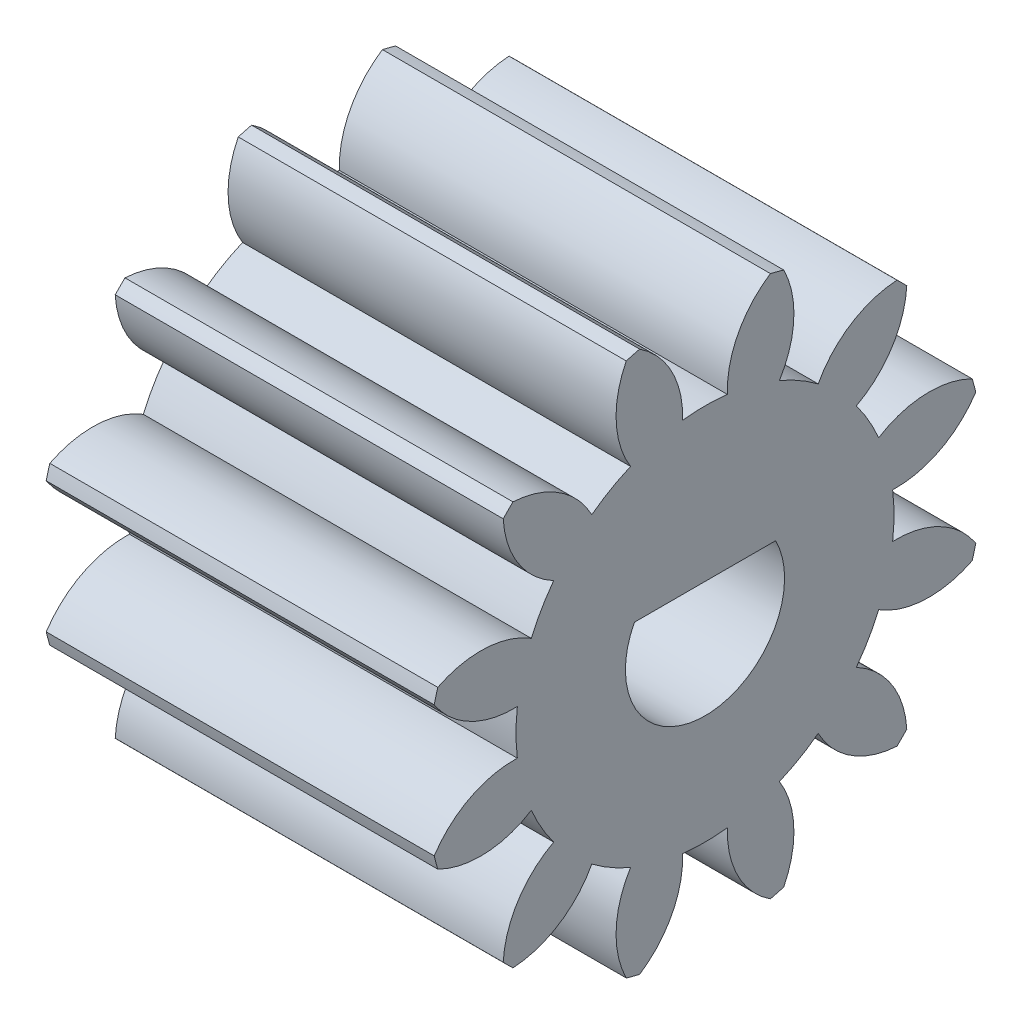
SolidWorks part; units mm, degrees
ref_plane "Plane1" through (0, 0, 0) normal (0, 0, 1) x (1, 0, 0)
ref_plane "Plane2" through (0, 0, 0) normal (0, 1, 0) x (1, 0, 0)
ref_plane "Plane3" through (0, 0, 0) normal (1, 0, 0) x (0, 0, -1)
sketch "HoldingSke" plane through (0, 0, 0) normal (0, 1, 0) x (1, 0, 0)
  line L0 (0, 0) -> (0.9781, -0.2079)
  line L1 (-15, 0) -> (100, 0) construction
  line L2 (0, 0) -> (-2.1039, 2.3779)
  line L3 (0, 0) -> (-11.863, 4.5341)
  line L4 (0, 0) -> (8.4473, 1.7955)
  line L5 (0, 0) -> (-46.8476, -17.4728)
  line L6 (0, 0) -> (-9.9476, -6.7116)
  line L7 (-2.1039, 2.3779) -> (8.6586, 51.2059)
  line L8 (-76.2, 54.61) -> (-76.1, 54.61)
  line L9 (-71.009, 38.7566) -> (-53.1078, 45.2721)
  line L10 (-76.2, 71.12) -> (104.1128, 71.12)
  line L11 (0, 0) -> (-12, 0)
  line L12 (-76.2, 101.6) -> (-76.162, 101.6)
  line L13 (24.9733, 27.94) -> (52.9518, 28.4284)
  line L14 (24.9733, 27.94) -> (24.9743, 27.94)
  line L15 (24.9733, 27.94) -> (100.4006, 29.5858)
  line L16 (-63.627, -1) -> (-12.827, -1)
  circle A0 centre (0, 0) radius 0.4
  circle A1 centre (0, 0) radius 4.749
  circle A2 centre (0, 0) radius 37.5
  circle A3 centre (0, 0) radius 0.4
  dimension "MHD" = 9.498
  dimension "Hub_dia" = 75
  dimension "Bore" = 0.8
  dimension "MBD" = 0.8
  dimension "Num_teeth" = 12
  dimension "Pitch" = 1
  dimension "Overall_len" = 50
  dimension "Show_teeth" = 12
  dimension "Thickness" = 12
  dimension "OAL" = 50.0001
  dimension "T_dim" = 0.1
  dimension "Ap" = 20
  dimension "H" = 19.05
  dimension "Pitch_radius" = 180.3128
  dimension "Width" = 12
  dimension "Backlash" = 0.038
  dimension "Addendum_fac" = 1
  dimension "Dedendum_fac" = 1.25
  dimension "Clearance_fac" = 0.25
  dimension "Dedendum_add" = 0.001
  dimension "Module" = 1
sketch "BasProSke" plane through (0, 0, 0) normal (0, 1, 0) x (1, 0, 0)
  line L0 (-10, 0) -> (60, 0) construction
  line L1 (0, 0) -> (0, 7)
  line L2 (0, 0) -> (9.75, 0)
  line L3 (9.75, 0) -> (9.75, 7)
  line L4 (9.75, 7) -> (0, 7)
  dimension "Thickness" = 9.75
  dimension "Diameter" = 14
revolve "Base-Revolve" add sketch "BasProSke" angle 360 about L0
sketch "TooCutSke" plane through (0, 0, 0) normal (1, 0, 0) x (0, 0, -1)
  line L1 (0, 0) -> (0, 107) construction
  line L2 (0, 0) -> (-0.8496, 5.9395) construction
  line L3 (0, 0) -> (-3.0836, 11.5081) construction
  line L4 (-0.8496, 5.9395) -> (-1.5418, 5.7541) construction
  arc A0 (0.5622, 4.7156) -> (-0.5622, 4.7156) centre (0, 0) ccw
  arc A1 (1.6729, 6.8233) -> (-1.6729, 6.8233) centre (0, 0) ccw
  circle A2 centre (0, 0) radius 6 construction
  circle A3 centre (0, 0) radius 5.6382 construction
  arc A4 (-0.5622, 4.7156) -> (-1.6729, 6.8233) centre (-2.9608, 4.7982) ccw
  arc A5 (1.6729, 6.8233) -> (0.5622, 4.7156) centre (2.9608, 4.7982) ccw
  dimension "Root_dia" = 9.498
  dimension "Overcut_dia" = 14.0508
  dimension "Pitch_dia" = 12
  dimension "Base_dia" = 11.2763
  dimension "Flank_rad" = 2.4
  dimension "Half_ang" = 15
  dimension "Half_CT" = 0.7167
extrude "ToothCut" cut sketch "TooCutSke" along normal through all
fillet "Breaks" [suppressed] radius 0.02 tangent propagation no
fillet "RootFillets" [suppressed] radius 0.251
pattern_circular "TeethCuts" count 12 every 30 about axis through (-10, 0, 0) along (1, 0, 0) of "ToothCut", "RootFillets", "Breaks"
sketch "HubNeaOneSke" plane through (0, 0, 0) normal (-1, 0, 0) x (0, 0, 1)
  circle A0 centre (0, 0) radius 4.749
  dimension "Diameter" = 9.498
extrude "HubNearOne" [suppressed] add sketch "HubNeaOneSke" along normal blind 40.2501
sketch "HubNeaBotSke" plane through (0, 0, 0) normal (-1, 0, 0) x (0, 0, 1)
  circle A0 centre (0, 0) radius 4.749
  dimension "Diameter" = 9.498
extrude "HubNearBoth" [suppressed] add sketch "HubNeaBotSke" along normal blind 20.125
ref_plane "FarPln" through (9.75, 0, 0) normal (1, 0, 0) x (0, 0, -1)
sketch "HubFarSke" plane through (9.75, 0, 0) normal (1, 0, 0) x (0, 0, -1)
  circle A0 centre (0, 0) radius 4.749
  dimension "Diameter" = 9.498
extrude "HubFar" [suppressed] add sketch "HubFarSke" along normal blind 20.125
sketch "BorSke" plane through (0, 0, 0) normal (1, 0, 0) x (0, 0, -1)
  circle A0 centre (0, 0) radius 0.4
  dimension "Diameter" = 0.8
extrude "Bore" cut sketch "BorSke" along normal mid plane 100.0001
sketch "KeySke" plane through (0, 0, 0) normal (1, 0, 0) x (0, 0, -1)
  line L0 (-0.05, 0) -> (-0.05, 0.5)
  line L1 (-0.05, 0.5) -> (0.05, 0.5)
  line L2 (0.05, 0.5) -> (0.05, 0)
  line L3 (0, 0) -> (0, 34) construction
  line L4 (-0.05, 0) -> (0.05, 0)
  dimension "Offset" = 0.5
  dimension "Width" = 0.1
extrude "Keyway" [suppressed] cut sketch "KeySke" along normal mid plane 100.0001
pattern_circular "Keyway2" [suppressed] count 2 every 90 about axis through (-10, 0, 0) along (1, 0, 0) reverse direction yes
sketch "Sketch1" plane through (0, 0, 0) normal (-1, 0, 0) x (0, 0, 1)
  circle A0 centre (0, 0) radius 7
scale "Scale1" scale about centroid uniform scaling yes scale factor 2
sketch "Sketch4" plane through (14.625, 0, 0) normal (1, 0, 0) x (0, 0, -1)
  line L2 (0, 1.85) -> (-3.5465, 1.85)
  line L3 (0, 1.85) -> (3.5465, 1.85)
  arc A0 (-3.5465, 1.85) -> (3.5465, 1.85) centre (0, 0) ccw
extrude "Cut-Extrude1" cut sketch "Sketch4" against normal blind 15
sketch "Sketch5" plane through (-4.875, 0, 0) normal (-1, 0, 0) x (0, 0, 1)
  circle A0 centre (0, 0) radius 4
extrude "Cut-Extrude2" cut sketch "Sketch5" against normal blind 5
equation "' \"Module@HoldingSke\" = 6.35"
equation "' \"Num_teeth@HoldingSke\" = 12"
equation "' \"Ap@HoldingSke\" =  20"
equation "' \"Ap@HoldingSke\" = 20"
equation "' \"Width@HoldingSke\" = 0.5 * 25.4"
equation "' \"Hub_dia@HoldingSke\"= 1 * 25.4"
equation "' \"Hub_dia@HoldingSke\" = 1 * 25.4"
equation "' \"Overall_len@HoldingSke\" = 1.0 * 25.4"
equation "' \"Bore@HoldingSke\" = 0.75 * 25.4"
equation "' \"T_dim@HoldingSke\" = 0.1 * 25.4"
equation "' \"Width@KeySke\" = 0.25 * 25.4"
equation "' \"Show_teeth@HoldingSke\" = 13"
equation "' \"Backlash@HoldingSke\" = 0.009 * 25.4"
equation "' \"Addendum_fac@HoldingSke\" = 1.0"
equation "' \"Dedendum_fac@HoldingSke\" = 1.25"
equation "' \"Dedendum_add@HoldingSke\" = 0.00005 * 25.4"
equation "' \"Clearance_fac@HoldingSke\" = 0.25"
equation "\"Pitch@HoldingSke\" = 1 / \"Module@HoldingSke\""
equation "\"Overcut_dia@TooCutSke\" = (\"Num_teeth@HoldingSke\" + 2 * \"Addendum_fac@HoldingSke\") / \"Pitch@HoldingSke\" + 0.002 * 25.4"
equation "\"Pitch_dia@TooCutSke\" = \"Num_teeth@HoldingSke\" / \"Pitch@HoldingSke\""
equation "\"Base_dia@TooCutSke\" = \"Num_teeth@HoldingSke\" / \"Pitch@HoldingSke\" * cos((\"Ap@HoldingSke\"  * 3.14159265 / 180))"
equation "\"Root_dia@TooCutSke\" = (\"Num_teeth@HoldingSke\" + 2) / \"Pitch@HoldingSke\" - 2 * (\"Addendum_fac@HoldingSke\" + \"Dedendum_fac@HoldingSke\") / \"Pitch@HoldingSke\" - \"Dedendum_add@HoldingSke\" * 2"
equation "\"Half_ang@TooCutSke\" = 180 / \"Num_teeth@HoldingSke\""
equation "\"Half_CT@TooCutSke\" = \"Num_teeth@HoldingSke\" / \"Pitch@HoldingSke\" * sin((3.14159265 / 2 / \"Num_teeth@HoldingSke\")) / 2 - 7 * \"Backlash@HoldingSke\" / 4"
equation "\"Flank_rad@TooCutSke\" = \"Num_teeth@HoldingSke\" / \"Pitch@HoldingSke\" / 5"
equation "\"Radius@RootFillets\" = \"Clearance_fac@HoldingSke\" / \"Pitch@HoldingSke\" + \"Dedendum_add@HoldingSke\""
equation "\"Break_rad@Breaks\" = 0.02 / \"Pitch@HoldingSke\""
equation "\"Thickness@HoldingSke\" = \"Width@HoldingSke\""
equation "\"OAL@HoldingSke\" = \"Thickness@HoldingSke\""
equation "\"MHD@HoldingSke\" = (\"Num_teeth@HoldingSke\" + 2) / \"Pitch@HoldingSke\" - 2 * (\"Addendum_fac@HoldingSke\" + \"Dedendum_fac@HoldingSke\")  / \"Pitch@HoldingSke\" - \"Dedendum_add@HoldingSke\" * 2"
equation "\"MBD@HoldingSke\" = (\"Num_teeth@HoldingSke\" + 2) / \"Pitch@HoldingSke\" - 2 * (\"Addendum_fac@HoldingSke\" + \"Dedendum_fac@HoldingSke\")  / \"Pitch@HoldingSke\" - \"Dedendum_add@HoldingSke\" * 2 - 0.002 * 25.4"
equation "\"MHD@HoldingSke\" = ((sgn( \"MHD@HoldingSke\" - \"Hub_dia@HoldingSke\" )-1)*( \"MHD@HoldingSke\" - \"Hub_dia@HoldingSke\" ))/-2+ \"Hub_dia@HoldingSke\""
equation "\"MBD@HoldingSke\" = ((sgn( \"MBD@HoldingSke\" - \"Bore@HoldingSke\" )-1)*( \"MBD@HoldingSke\" - \"Bore@HoldingSke\" ))/-2+ \"Bore@HoldingSke\""
equation "\"OAL@HoldingSke\" = ((sgn( \"OAL@HoldingSke\" - \"Overall_len@HoldingSke\" )+1)*( \"OAL@HoldingSke\" - \"Overall_len@HoldingSke\" ))/2 + \"Overall_len@HoldingSke\" + 0.000002 * 25.4"
equation "\"Num_teeth@TeethCuts\" = int( \"Show_teeth@HoldingSke\" ) + 1"
equation "\"Num_teeth@TeethCuts\" = ((sgn( \"Num_teeth@TeethCuts\" - \"Num_teeth@HoldingSke\" )-1)*( \"Num_teeth@TeethCuts\" - \"Num_teeth@HoldingSke\" ))/-2+ \"Num_teeth@HoldingSke\""
equation "\"Num_teeth@TeethCuts\" = ((sgn( \"Num_teeth@TeethCuts\" - 2.0)+1)*( \"Num_teeth@TeethCuts\" - 2.0))/2 +2.0"
equation "\"Angle@TeethCuts\" = 360.0 / \"Num_teeth@HoldingSke\""
equation "\"Diameter@BasProSke\" = (\"Num_teeth@HoldingSke\" + 2 * \"Addendum_fac@HoldingSke\") / \"Pitch@HoldingSke\""
equation "' \"Fillet_rad@BasProSke\" =  \"Thickness@HoldingSke\" * 0.05"
equation "' \"Fillet_rad@BasProSke\" = \"Thickness@HoldingSke\" * 0.05"
equation "\"MHD@HoldingSke\" = ((sgn( \"MHD@HoldingSke\" - \"Root_dia@TooCutSke\" )-1)*( \"MHD@HoldingSke\" - \"Root_dia@TooCutSke\" ))/-2+ \"Root_dia@TooCutSke\""
equation "\"Diameter@HubNeaOneSke\" = \"MHD@HoldingSke\""
equation "\"Length@HubNearOne\" = \"OAL@HoldingSke\" - \"Thickness@BasProSke\""
equation "\"Diameter@HubNeaBotSke\" = \"MHD@HoldingSke\""
equation "\"Length@HubNearBoth\" = ( \"OAL@HoldingSke\" - \"Thickness@BasProSke\" ) / 2.0"
equation "\"Thickness@FarPln\" = \"Thickness@BasProSke\""
equation "\"Diameter@HubFarSke\" = \"MHD@HoldingSke\""
equation "\"Length@HubFar\" = ( \"OAL@HoldingSke\" - \"Thickness@BasProSke\" ) / 2.0"
equation "\"Diameter@BorSke\" = \"MBD@HoldingSke\""
equation "\"D1@Bore\" = \"OAL@HoldingSke\" * 2.0"
equation "\"D1@Keyway\" = \"OAL@HoldingSke\" * 2.0"
equation "\"Offset@KeySke\" = \"T_dim@HoldingSke\" + \"MBD@HoldingSke\" / 2.0"
